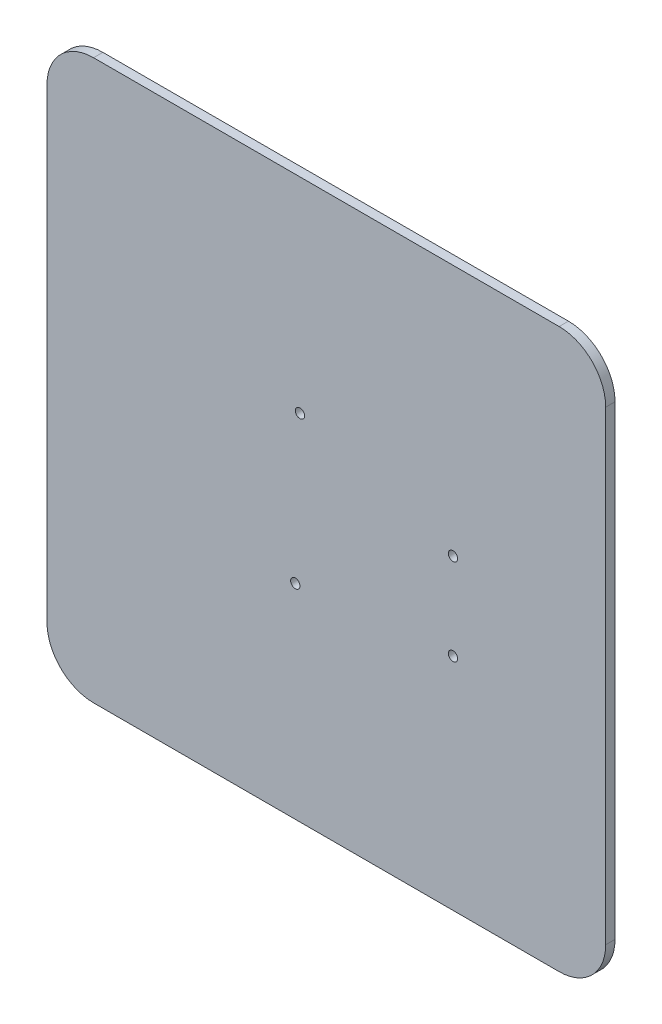
SolidWorks part; units mm, degrees
ref_plane "Front" through (0, 0, 0) normal (0, 0, 1) x (1, 0, 0)
ref_plane "Top" through (0, 0, 0) normal (0, 1, 0) x (1, 0, 0)
ref_plane "Right" through (0, 0, 0) normal (1, 0, 0) x (0, 0, -1)
sketch "Эскиз1" plane through (0, 0, 0) normal (0, 0, 1) x (1, 0, 0)
  line L1 (75, -90) -> (-75, -90)
  line L2 (90, -75) -> (90, 75)
  line L3 (75, 90) -> (-75, 90)
  line L4 (-90, -75) -> (-90, 75)
  line L5 (90, -90) -> (-90, 90) construction
  line L6 (90, 90) -> (-90, -90) construction
  arc A0 (-75, -90) -> (-90, -75) centre (-75, -75) cw
  arc A1 (75, -90) -> (90, -75) centre (75, -75) ccw
  arc A2 (90, 75) -> (75, 90) centre (75, 75) ccw
  arc A3 (-90, 75) -> (-75, 90) centre (-75, 75) cw
  point P0 (0, 0)
  dimension "D3" = 15
  dimension "D1" = 180
  dimension "D2" = 180
extrude "Бобышка-Вытянуть1" add sketch "Эскиз1" along normal blind 3
hole_wizard "Диаметр отверстия Ø3.0 (3)1" positions "Эскиз5" profile "Эскиз4" hole size "Ø3.0" standard "Ansi Metric" end condition up to next
sketch "Эскиз5" plane through (0, 0, 3) normal (0, 0, 1) x (1, 0, 0)
  line L4 (-90, 0) -> (-10, 0) construction
  line L5 (-90, 75) -> (-90, -75) construction
  line L6 (-10, 0) -> (40.8, 0) construction
  line L7 (40.8, 0) -> (90, 0) construction
  line L8 (90, -75) -> (90, 75) construction
  line L10 (-10, -26.65) -> (-10, 26.65) construction
  line L12 (40.8, -19.05) -> (40.8, 8.85) construction
  line L13 (-10, 24.05) -> (-8.5, 24.05) construction
  point P33 (-10, -24.15)
  point P45 (40.8, 8.85)
  point P48 (40.8, -19.05)
  point P59 (-8.5, 24.05)
  dimension "D1" = 53.3
  dimension "D2" = 50.8
  dimension "D3" = 27.9
  dimension "D4" = 2.5
  dimension "D5" = 5.1
  dimension "D6" = 1.5
  dimension "D7" = 80
  dimension "D8" = 15.2
sketch "Эскиз4" plane through (-10, -24.15, 3) normal (1, 0, 0) x (0, -1, 0)
  line L0 (0, 0) -> (0, 3)
  line L1 (0, 3) -> (1.5, 3)
  line L2 (1.5, 3) -> (1.5, 0)
  line L5 (1.5, 0) -> (0, 0)
  line L11 (0, -6.35) -> (0, 107.95) construction
  dimension "Диаметр сквозного отверстия" = 3
  dimension "Глубина сквозного отверстия" = 3
